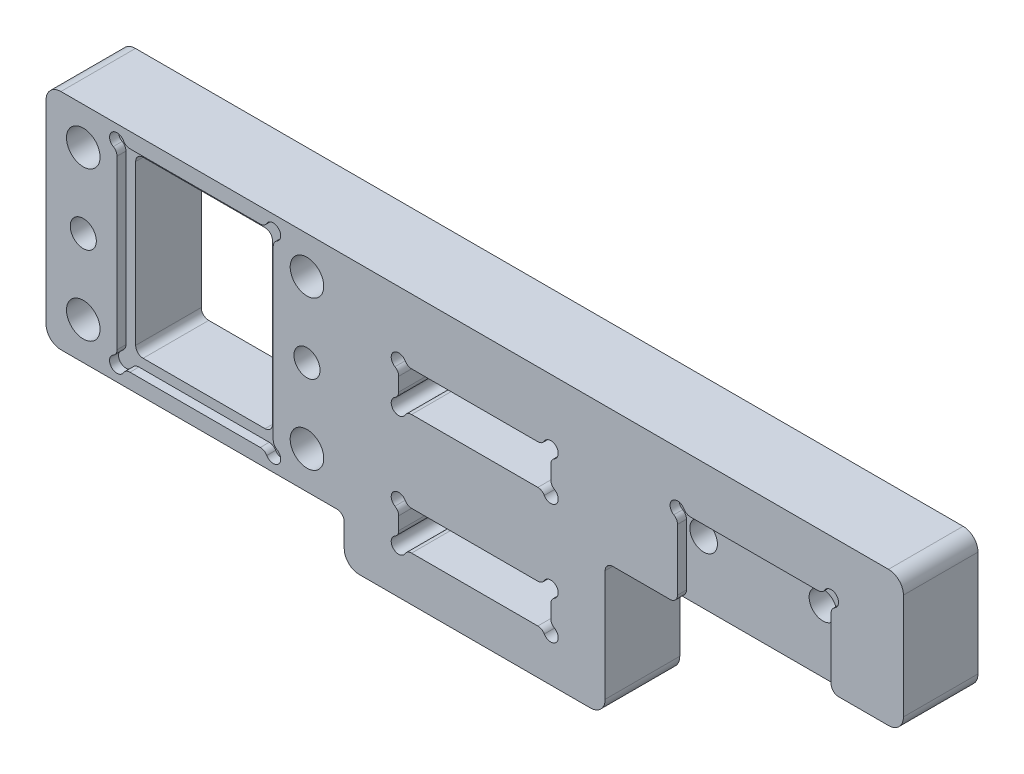
SolidWorks part; units mm, degrees
ref_plane "Přední rovina" through (0, 0, 0) normal (0, 0, 1) x (1, 0, 0)
ref_plane "Horní rovina" through (0, 0, 0) normal (0, 1, 0) x (1, 0, 0)
ref_plane "Pravá rovina" through (0, 0, 0) normal (1, 0, 0) x (0, 0, -1)
sketch "Skica1" plane through (0, 0, 0) normal (0, 0, 1) x (1, 0, 0)
  line L1 (-10.2, 11.2) -> (10.2, 11.2)
  line L2 (-10.2, 11.2) -> (-10.2, 6)
  line L3 (-10.2, 6) -> (10.2, 6)
  line L4 (10.2, 11.2) -> (10.2, 6)
  line L5 (-57.5, 36.1) -> (57.5, 36.1)
  line L6 (-57.5, 36.1) -> (-57.5, 6.1)
  line L7 (-17.5, 0) -> (17.5, 0)
  line L8 (57.5, 36.1) -> (57.5, 17.95)
  line L14 (-52.5, 31.1) -> (-22.5, 31.1) construction
  line L15 (-57.5, 6.1) -> (-17.5, 6.1)
  line L16 (-17.5, 6.1) -> (-17.5, 0)
  line L17 (17.5, 0) -> (17.5, 17.95)
  line L18 (17.5, 17.95) -> (57.5, 17.95)
  line L19 (-52.5, 31.1) -> (-52.5, 11.1) construction
  line L20 (-52.5, 11.1) -> (-22.5, 11.1) construction
  line L21 (-22.5, 31.1) -> (-22.5, 11.1) construction
  line L22 (-10.2, 27.4) -> (10.2, 27.4)
  line L23 (-10.2, 27.4) -> (-10.2, 22.1)
  line L24 (-10.2, 22.1) -> (10.2, 22.1)
  line L25 (10.2, 27.4) -> (10.2, 22.1)
  circle A4 centre (-52.5, 31.1) radius 2.25
  circle A5 centre (-22.5, 31.1) radius 2.25
  circle A6 centre (-52.5, 11.1) radius 2.25
  circle A7 centre (-22.5, 11.1) radius 2.25
  circle A8 centre (-52.5, 21.1) radius 1.75
  circle A9 centre (-22.5, 21.1) radius 1.75
  point P8 (10.2, 8.6)
  point P10 (-37.5, 11.1)
  point P15 (-52.5, 21.1)
  point P16 (-57.5, 21.1)
  point P17 (-10.2, 8.6)
  point P18 (0, 0)
  point P20 (0, 22.1)
  point P35 (0, 21.1)
  point P37 (0, 6)
  dimension "D13" = 3.5
  dimension "D18" = 1
  dimension "D9" = 4.5
  dimension "D1" = 20.4
  dimension "D2" = 5.2
  dimension "D3" = 30
  dimension "D4" = 40
  dimension "D5" = 35
  dimension "D6" = 20
  dimension "D7" = 30
  dimension "D8" = 20
  dimension "D10" = 12.5
  dimension "D11" = 5.3
  dimension "D12" = 20.4
  dimension "D14" = 40
  dimension "D15" = 9.35
  dimension "D16" = 7.3
  dimension "D17" = 6
  dimension "D19" = 12.5
extrude "Přidat vysunutím1" add sketch "Skica1" against normal blind 10 contours L17 L18 L8 L5 L6 L15 L16 L7 region at (-5.0711, 21.5768, 0)
sketch "Skica2" plane through (0, 0, 0) normal (0, 0, 1) x (1, 0, 0)
  line L0 (17.5, 17.95) -> (57.5, 17.95) construction
  line L1 (27.2, 28.9) -> (47.8, 28.9)
  line L2 (27.2, 28.9) -> (27.2, 17.95)
  line L3 (27.2, 17.95) -> (47.8, 17.95)
  line L4 (47.8, 28.9) -> (47.8, 17.95)
  line L6 (29.5, 26.35) -> (45.5, 26.35) construction
  line L7 (27.5, 28.6) -> (47.5, 28.6) construction
  line L8 (27.5, 28.6) -> (27.5, 12.95) construction
  line L9 (27.5, 12.95) -> (47.5, 12.95) construction
  line L10 (47.5, 28.6) -> (47.5, 12.95) construction
  line L12 (57.5, 36.1) -> (57.5, 17.95) construction
  circle A0 centre (29.5, 26.35) radius 1.85 construction
  circle A1 centre (45.5, 26.35) radius 1.85 construction
  point P6 (37.5, 17.95)
  point P14 (37.5, 28.6)
  point P15 (37.5, 26.35)
  point P18 (37.5, 28.9)
  dimension "D9" = 3.7
  dimension "D2" = 0.3
  dimension "D4" = 20
  dimension "D5" = 15.65
  dimension "D6" = 5
  dimension "D7" = 16
  dimension "D8" = 2.25
  dimension "D10" = 0.3
  dimension "D11" = 37.5
  dimension "D12" = 9.7
extrude "Odebrat vysunutím1" cut sketch "Skica2" against normal blind 1.2
sketch "Skica4" plane through (0, 0, -1.2) normal (0, 0, 1) x (1, 0, 0)
  circle A0 centre (45.5, 26.35) radius 1.85 construction
  circle A1 centre (29.5, 26.35) radius 1.85 construction
  circle A2 centre (45.5, 26.35) radius 1.85
  circle A3 centre (29.5, 26.35) radius 1.85
extrude "Odebrat vysunutím2" cut sketch "Skica4" against normal through all
sketch "Skica5" plane through (0, 0, 0) normal (0, 0, 1) x (1, 0, 0)
  line L0 (-52.5, 31.1) -> (-22.5, 31.1) construction
  line L1 (-47.975, 34.075) -> (-27.025, 34.075)
  line L2 (-47.975, 34.075) -> (-47.975, 8.125)
  line L3 (-47.975, 8.125) -> (-27.025, 8.125)
  line L4 (-27.025, 34.075) -> (-27.025, 8.125)
  line L5 (-46.675, 32.775) -> (-28.325, 32.775)
  line L6 (-46.675, 32.775) -> (-46.675, 9.425)
  line L7 (-46.675, 9.425) -> (-28.325, 9.425)
  line L8 (-28.325, 32.775) -> (-28.325, 9.425)
  line L10 (-47.675, 33.775) -> (-27.325, 33.775) construction
  line L11 (-47.675, 33.775) -> (-47.675, 8.425) construction
  line L12 (-47.675, 8.425) -> (-27.325, 8.425) construction
  line L13 (-27.325, 33.775) -> (-27.325, 8.425) construction
  point P8 (-37.5, 32.775)
  point P9 (-37.5, 34.075)
  point P10 (-47.975, 21.1)
  point P11 (-46.675, 21.1)
  point P17 (-37.5, 31.1)
  point P20 (-37.5, 33.775)
  point P21 (-47.675, 21.1)
  dimension "D1" = 18.35
  dimension "D2" = 23.35
  dimension "D3" = 0.3
  dimension "D4" = 0.3
  dimension "D7" = 20.35
  dimension "D8" = 25.35
extrude "Odebrat vysunutím3" cut sketch "Skica5" against normal through all and the other way through all contours L6 L7 L8 L5
extrude "Odebrat vysunutím4" cut sketch "Skica5<3>" against normal blind 1.2 contours L1 L4 L3 L2
sketch "Skica5<3>" plane through (0, 0, 0) normal (0, 0, 1) x (1, 0, 0) same geometry as "Skica5"
sketch "Skica6" plane through (0, 0, 0) normal (0, 0, 1) x (1, 0, 0)
  circle A0 centre (-47.975, 34.075) radius 1
  circle A1 centre (-27.025, 34.075) radius 1
  circle A2 centre (-47.975, 8.125) radius 1
  circle A3 centre (-27.025, 8.125) radius 1
  circle A4 centre (27.2, 28.9) radius 1
  circle A5 centre (47.8, 28.9) radius 1
  dimension "D1" = 2
extrude "Odebrat vysunutím5" cut sketch "Skica6" against normal up to surface (1.2 mm away) up to face at (-37.5, 21.1, -1.2)
sketch "Skica7" plane through (0, 0, 0) normal (0, 0, 1) x (1, 0, 0)
  circle A0 centre (-10.2, 27.4) radius 1
  circle A1 centre (-10.2, 22.1) radius 1
  circle A2 centre (10.2, 22.1) radius 1
  circle A3 centre (10.2, 27.4) radius 1
  circle A4 centre (-10.2, 11.2) radius 1
  circle A5 centre (-10.2, 6) radius 1
  circle A6 centre (10.2, 6) radius 1
  circle A7 centre (10.2, 11.2) radius 1
  dimension "D1" = 2
extrude "Odebrat vysunutím6" cut sketch "Skica7" against normal through all
ref_axis "Osa1" through (0, 21.1, -5.5476) along (0, 0, 1)
fillet "Zaoblit3" radius 2 6 edges at (17.5, 0, -5) (-17.5, 0, -5) (-57.5, 6.1, -5) (57.5, 17.95, -5) (57.5, 36.1, -5) (-57.5, 36.1, -5)
fillet "Zaoblit4" radius 1 2 edges at (17.5, 17.95, -5) (-17.5, 6.1, -5)
fillet "Zaoblit5" radius 1 18 edges at (47.8, 17.95, -0.6) (27.2, 17.95, -0.6) (47.8, 27.9, -0.6) (46.8, 28.9, -0.6) (28.2, 28.9, -0.6) (27.2, 27.9, -0.6) (-28.325, 9.425, -5.6) (-27.025, 9.125, -0.6) (-28.025, 8.125, -0.6) (-46.675, 9.425, -5.6) (-47.975, 9.125, -0.6) (-46.975, 8.125, -0.6) (-28.325, 32.775, -5.6) (-28.025, 34.075, -0.6) (-27.025, 33.075, -0.6) (-46.675, 32.775, -5.6) (-46.975, 34.075, -0.6) (-47.975, 33.075, -0.6)
fillet "Zaoblit6" radius 1 16 edges at (-10.2, 7, -5) (-9.2, 6, -5) (9.2, 6, -5) (10.2, 7, -5) (10.2, 10.2, -5) (9.2, 11.2, -5) (-9.2, 11.2, -5) (-10.2, 10.2, -5) (10.2, 26.4, -5) (-10.2, 23.1, -5) (-9.2, 22.1, -5) (9.2, 22.1, -5) (10.2, 23.1, -5) (9.2, 27.4, -5) (-9.2, 27.4, -5) (-10.2, 26.4, -5)
